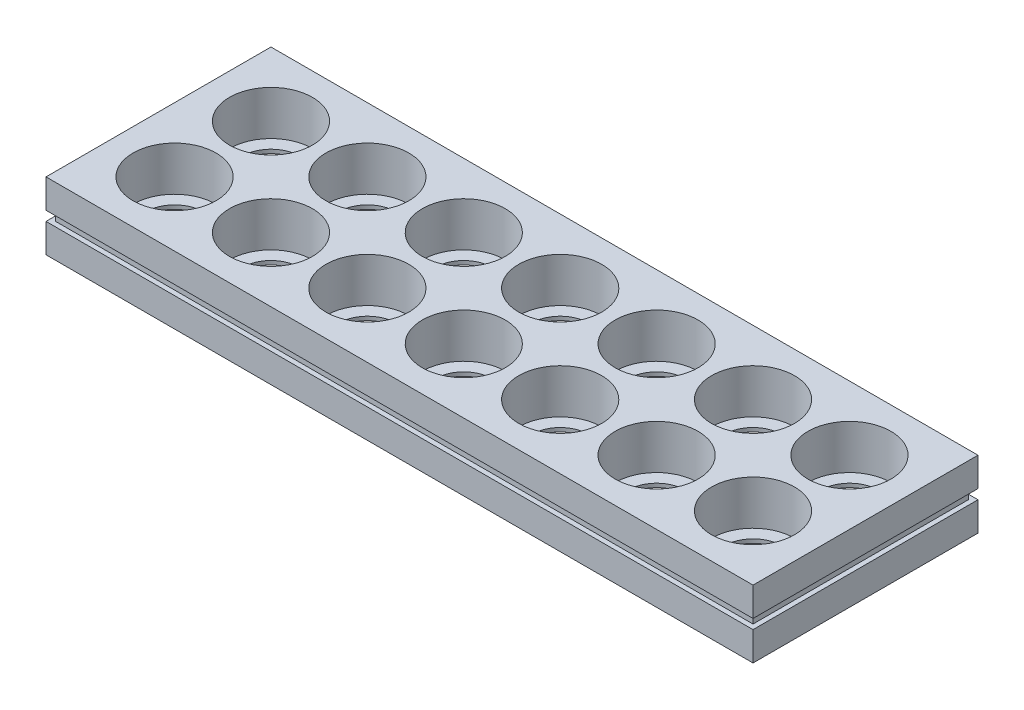
SolidWorks part; units mm, degrees
ref_plane "Front Plane" through (0, 0, 0) normal (0, 0, 1) x (1, 0, 0)
ref_plane "Top Plane" through (0, 0, 0) normal (0, 1, 0) x (1, 0, 0)
ref_plane "Right Plane" through (0, 0, 0) normal (1, 0, 0) x (0, 0, -1)
sketch "Sketch1" plane through (0, 0, 0) normal (0, 1, 0) x (1, 0, 0)
  line L1 (-16.9333, -16.9333) -> (169.3333, -16.9333)
  line L2 (-16.9333, -16.9333) -> (-16.9333, 42.3333)
  line L3 (-16.9333, 42.3333) -> (169.3333, 42.3333)
  line L4 (169.3333, -16.9333) -> (169.3333, 42.3333)
  line L5 (-14.3933, 39.7933) -> (166.7933, 39.7933)
  line L6 (-14.3933, 39.7933) -> (-14.3933, -14.3933)
  line L7 (-14.3933, -14.3933) -> (166.7933, -14.3933)
  line L8 (166.7933, 39.7933) -> (166.7933, -14.3933)
  circle A0 centre (0, 0) radius 10.922
  circle A1 centre (0, 0) radius 7.5
  circle A2 centre (25.4, 0) radius 10.922
  circle A3 centre (25.4, 0) radius 7.5
  circle A4 centre (50.8, 0) radius 10.922
  circle A5 centre (50.8, 0) radius 7.5
  circle A6 centre (76.2, 0) radius 10.922
  circle A7 centre (76.2, 0) radius 7.5
  circle A8 centre (101.6, 0) radius 10.922
  circle A9 centre (101.6, 0) radius 7.5
  circle A10 centre (127, 0) radius 10.922
  circle A11 centre (127, 0) radius 7.5
  circle A12 centre (152.4, 0) radius 10.922
  circle A13 centre (152.4, 0) radius 7.5
  circle A14 centre (25.4, 25.4) radius 10.922
  circle A15 centre (25.4, 25.4) radius 7.5
  circle A16 centre (50.8, 25.4) radius 10.922
  circle A17 centre (50.8, 25.4) radius 7.5
  circle A18 centre (76.2, 25.4) radius 10.922
  circle A19 centre (76.2, 25.4) radius 7.5
  circle A20 centre (101.6, 25.4) radius 10.922
  circle A21 centre (101.6, 25.4) radius 7.5
  circle A22 centre (127, 25.4) radius 10.922
  circle A23 centre (127, 25.4) radius 7.5
  circle A24 centre (152.4, 25.4) radius 10.922
  circle A25 centre (152.4, 25.4) radius 7.5
  circle A26 centre (0, 25.4) radius 10.922
  circle A27 centre (0, 25.4) radius 7.5
  dimension "D1" = 21.844
  dimension "D2" = 15
  dimension "D5" = 16.9333
  dimension "D7" = 16.9333
  dimension "D8" = 16.9333
  dimension "D6" = 16.9333
  dimension "D9" = 2.54
  dimension "D10" = 2.54
  dimension "D11" = 2.54
  dimension "D12" = 2.54
  dimension "D3" = 7
  dimension "D4" = 2
extrude "Boss-Extrude2" add sketch "Sketch1" along normal blind 12.7 contours L1 L4 L3 L2 A26 A24 A22 A20 A18 A16 A14 A12 A10 A8 A6 A4 A2 A0 | L1 L4 L3 L2 L5 L8 L7 L6 region at (-14.9787, 0, -12.7) region at (76.2, 0, -12.7)
extrude "Boss-Extrude3" add sketch "Sketch1<4>" along normal blind 1.016 contours A26 A27 | A14 A15 | A16 A17 | A18 A19 | A20 A21 | A22 A23 | A24 A25 | A0 A1 | A2 A3 | A4 A5 | A6 A7 | A8 A9 | A10 A11 | A12 A13 region at (-10.6131, 0, 0) region at (14.7869, 0, 0) region at (40.1869, 0, 0) region at (65.5869, 0, 0) region at (90.9869, 0, 0) region at (116.3869, 0, 0) region at (141.7869, 0, 0) region at (14.7869, 0, -25.4) region at (40.1869, 0, -25.4) region at (65.5869, 0, -25.4) region at (90.9869, 0, -25.4) region at (116.3869, 0, -25.4) region at (141.7869, 0, -25.4) region at (-10.6131, 0, -25.4)
sketch "Sketch1<4>" plane through (0, 0, 0) normal (0, 1, 0) x (1, 0, 0) same geometry as "Sketch1"
extrude "Boss-Extrude4" add sketch "Sketch1<6>" against normal blind 5.08 contours L1 L4 L3 L2 L5 L8 L7 L6 region at (-14.9787, 0, -12.7)
sketch "Sketch1<6>" plane through (0, 0, 0) normal (0, 1, 0) x (1, 0, 0) same geometry as "Sketch1"
sketch "Sketch2" plane through (0, 0, 16.9333) normal (0, 0, 1) x (1, 0, 0)
  line L0 (-16.9333, 12.7) -> (169.3333, 12.7) construction
  line L1 (-16.9333, 2.54) -> (169.3333, 2.54)
  line L2 (-16.9333, 2.54) -> (-16.9333, 5.08)
  line L3 (-16.9333, 5.08) -> (169.3333, 5.08)
  line L4 (169.3333, 2.54) -> (169.3333, 5.08)
  line L5 (-16.9333, 2.54) -> (169.3333, 5.08) construction
  line L6 (-16.9333, 5.08) -> (169.3333, 2.54) construction
  line L7 (169.3333, 12.7) -> (169.3333, -5.08) construction
  line L8 (-16.9333, 12.7) -> (-16.9333, -5.08) construction
  point P0 (76.2, 3.81)
  point P5 (70.6705, 2.6211)
  point P6 (71.3677, 1.1461)
  point P9 (0, 0)
  point P10 (0, 0)
  point P11 (76.2, 12.7)
  point P14 (169.3333, 3.81)
  point P17 (-16.9333, 3.81)
  dimension "D1" = 7.62
  dimension "D2" = 0
extrude "Cut-Extrude1" cut sketch "Sketch2" against normal blind 1.27
sketch "Sketch6" plane through (169.3333, 0, 0) normal (1, 0, 0) x (0, 0, -1)
  line L0 (-16.9333, 12.7) -> (42.3333, 12.7) construction
  line L1 (-16.9333, 2.54) -> (42.3333, 2.54)
  line L2 (-16.9333, 2.54) -> (-16.9333, 5.08)
  line L3 (-16.9333, 5.08) -> (42.3333, 5.08)
  line L4 (42.3333, 2.54) -> (42.3333, 5.08)
  line L5 (-16.9333, 2.54) -> (42.3333, 5.08) construction
  line L6 (-16.9333, 5.08) -> (42.3333, 2.54) construction
  line L7 (42.3333, 12.7) -> (42.3333, -5.08) construction
  line L8 (-16.9333, 12.7) -> (-16.9333, 5.08) construction
  point P0 (12.7, 3.81)
  point P5 (0, 0)
  point P8 (12.7, 12.7)
  point P11 (42.3333, 3.81)
  dimension "D1" = 0
  dimension "D2" = 7.62
sketch "Sketch7" plane through (0, 0, -42.3333) normal (0, 0, -1) x (-1, 0, 0)
  line L0 (16.9333, 12.7) -> (-169.3333, 12.7) construction
  line L1 (-169.3333, 2.54) -> (16.9333, 2.54)
  line L2 (-169.3333, 2.54) -> (-169.3333, 5.08)
  line L3 (-169.3333, 5.08) -> (16.9333, 5.08)
  line L4 (16.9333, 2.54) -> (16.9333, 5.08)
  line L5 (-169.3333, 2.54) -> (16.9333, 5.08) construction
  line L6 (-169.3333, 5.08) -> (16.9333, 2.54) construction
  line L7 (16.9333, 12.7) -> (16.9333, -5.08) construction
  line L8 (-169.3333, 12.7) -> (-169.3333, -5.08) construction
  point P0 (-76.2, 3.81)
  point P7 (-76.2, 12.7)
  point P10 (16.9333, 3.81)
  dimension "D1" = 7.62
  dimension "D2" = 0
sketch "Sketch8" plane through (-16.9333, 0, 0) normal (-1, 0, 0) x (0, 0, 1)
  line L1 (-42.3333, 2.54) -> (16.9333, 2.54)
  line L2 (-42.3333, 2.54) -> (-42.3333, 5.08)
  line L3 (-42.3333, 5.08) -> (16.9333, 5.08)
  line L4 (16.9333, 2.54) -> (16.9333, 5.08)
  line L5 (-42.3333, 2.54) -> (16.9333, 5.08) construction
  line L6 (-42.3333, 5.08) -> (16.9333, 2.54) construction
  point P0 (-12.7, 3.81)
extrude "Cut-Extrude5" cut sketch "Sketch6" against normal blind 1.27
extrude "Cut-Extrude6" cut sketch "Sketch7" against normal blind 1.27
extrude "Cut-Extrude7" cut sketch "Sketch8" against normal blind 1.27
